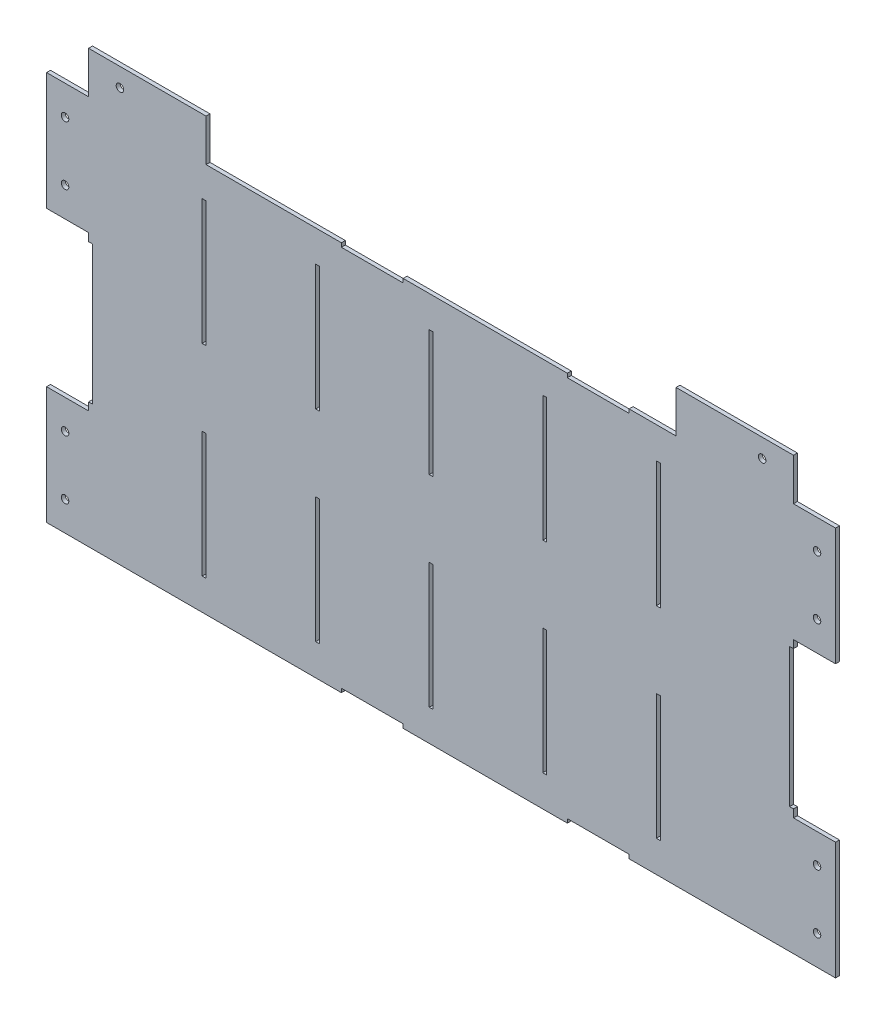
SolidWorks part; units mm, degrees
material "6061-T6 (SS)"
ref_plane "X-Y Datum" through (0, 0, 0) normal (0, 0, 1) x (1, 0, 0)
ref_plane "X-Z Datum" through (0, 0, 0) normal (0, 1, 0) x (1, 0, 0)
ref_plane "Y-Z Datum" through (0, 0, 0) normal (1, 0, 0) x (0, 0, -1)
sketch "Sketch1" plane through (0, 0, 0) normal (0, 0, 1) x (1, 0, 0)
  line L0 (-285.4305, 0) -> (285.4305, 0) construction
  line L1 (-285.4305, -157.7875) -> (285.4305, -157.7875)
  line L2 (-285.4305, -157.7875) -> (-285.4305, 157.7875)
  line L3 (-285.4305, 157.7875) -> (285.4305, 157.7875)
  line L4 (285.4305, -157.7875) -> (285.4305, 157.7875)
  line L5 (-285.4305, -157.7875) -> (285.4305, 157.7875) construction
  line L6 (-285.4305, 157.7875) -> (285.4305, -157.7875) construction
  line L7 (-282.2555, -154.615) -> (-282.2555, 154.615)
  line L8 (-280.6655, -153.025) -> (-195.0655, -153.025)
  line L9 (-280.6655, -153.025) -> (-280.6655, 153.025)
  line L10 (-280.6655, 153.025) -> (-195.0655, 153.025)
  line L11 (-195.0655, -153.025) -> (-195.0655, 153.025)
  line L12 (-280.6655, -153.025) -> (-195.0655, 153.025) construction
  line L13 (-280.6655, 153.025) -> (-195.0655, -153.025) construction
  line L14 (-282.2555, 154.615) -> (-193.4755, 154.615)
  line L15 (-193.4755, -154.615) -> (-193.4755, 154.615)
  line L16 (-282.2555, -154.615) -> (-193.4755, -154.615)
  line L17 (-190.3005, 154.615) -> (-101.5205, 154.615)
  line L18 (-188.7105, 153.025) -> (-103.1105, 153.025)
  line L19 (-190.3005, -154.615) -> (-190.3005, 154.615)
  line L20 (-188.7105, -153.025) -> (-188.7105, 153.025)
  line L21 (-101.5205, -154.615) -> (-101.5205, 154.615)
  line L22 (-103.1105, -153.025) -> (-103.1105, 153.025)
  line L23 (-188.7105, -153.025) -> (-103.1105, -153.025)
  line L24 (-190.3005, -154.615) -> (-101.5205, -154.615)
  line L25 (-188.7105, -153.025) -> (-103.1105, 153.025) construction
  line L26 (-188.7105, 153.025) -> (-103.1105, -153.025) construction
  line L27 (-98.3455, 154.615) -> (-9.5655, 154.615)
  line L28 (-96.7555, 153.025) -> (-11.1555, 153.025)
  line L29 (-98.3455, -154.615) -> (-98.3455, 154.615)
  line L30 (-96.7555, -153.025) -> (-96.7555, 153.025)
  line L31 (-9.5655, -154.615) -> (-9.5655, 154.615)
  line L32 (-11.1555, -153.025) -> (-11.1555, 153.025)
  line L33 (-96.7555, -153.025) -> (-11.1555, -153.025)
  line L34 (-98.3455, -154.615) -> (-9.5655, -154.615)
  line L35 (-96.7555, -153.025) -> (-11.1555, 153.025) construction
  line L36 (-96.7555, 153.025) -> (-11.1555, -153.025) construction
  line L37 (-6.3905, 154.615) -> (82.3895, 154.615)
  line L38 (-4.8005, 153.025) -> (80.7995, 153.025)
  line L39 (-6.3905, -154.615) -> (-6.3905, 154.615)
  line L40 (-4.8005, -153.025) -> (-4.8005, 153.025)
  line L41 (82.3895, -154.615) -> (82.3895, 154.615)
  line L42 (80.7995, -153.025) -> (80.7995, 153.025)
  line L43 (-4.8005, -153.025) -> (80.7995, -153.025)
  line L44 (-6.3905, -154.615) -> (82.3895, -154.615)
  line L45 (-4.8005, -153.025) -> (80.7995, 153.025) construction
  line L46 (-4.8005, 153.025) -> (80.7995, -153.025) construction
  line L47 (85.5645, 154.615) -> (174.3445, 154.615)
  line L48 (87.1545, 153.025) -> (172.7545, 153.025)
  line L49 (85.5645, -154.615) -> (85.5645, 154.615)
  line L50 (87.1545, -153.025) -> (87.1545, 153.025)
  line L51 (174.3445, -154.615) -> (174.3445, 154.615)
  line L52 (172.7545, -153.025) -> (172.7545, 153.025)
  line L53 (87.1545, -153.025) -> (172.7545, -153.025)
  line L54 (85.5645, -154.615) -> (174.3445, -154.615)
  line L55 (87.1545, -153.025) -> (172.7545, 153.025) construction
  line L56 (87.1545, 153.025) -> (172.7545, -153.025) construction
  point P0 (0, 0)
  point P8 (-237.8655, 0)
  point P17 (-145.9105, 0)
  dimension "D1" = 570.861
  dimension "D2" = 315.575
  dimension "D3" = 306.05
  dimension "D4" = 85.6
  dimension "D5" = 3.175
  dimension "D8" = 3.175
  dimension "D9" = 91.955
  dimension "D6" = 1.59
  dimension "D7" = 5
extrude "Boss-Extrude1" add sketch "Sketch1" along normal blind 3.175 contours L8 L11 L10 L9 | L20 L23 L22 L18 | L30 L33 L32 L28 | L50 L53 L52 L48 | L49 L54 L51 L47 L53 L50 L48 L52 | L1 L4 L3 L2 L54 L49 L47 L51 L44 L39 L37 L41 L34 L29 L27 L31 L24 L19 L17 L21 L16 L7 L14 L15 | L40 L43 L42 L38 | L7 L16 L15 L14 L11 L8 L9 L10 | L19 L24 L21 L17 L23 L20 L18 L22 | L29 L34 L31 L27 L33 L30 L28 L32 | L39 L44 L41 L37 L43 L40 L38 L42 region at (-284.7782, 0, 0) region at (-281.9338, 0, 0) region at (-237.8655, 0, 0) region at (-145.9105, 154.2933, 0) region at (-145.9105, 0, 0) region at (-53.9555, 154.2933, 0) region at (-53.9555, 0, 0) region at (37.9995, 154.2933, 0) region at (37.9995, 0, 0) region at (129.9545, 154.2933, 0) region at (129.9545, 0, 0)
sketch "Sketch2" plane through (0, 0, 3.175) normal (0, 0, 1) x (1, 0, 0)
  line L0 (-190.3005, -154.615) -> (-193.4755, -154.615) construction
  line L1 (-191.888, -154.615) -> (-191.888, 157.7875) construction
  line L2 (-285.4305, 157.7875) -> (285.4305, 157.7875) construction
  line L4 (-193.4755, -30.7875) -> (-190.3005, -30.7875)
  line L5 (-193.4755, -30.7875) -> (-193.4755, -132.3875)
  line L6 (-193.4755, -132.3875) -> (-190.3005, -132.3875)
  line L7 (-190.3005, -30.7875) -> (-190.3005, -132.3875)
  line L8 (-193.4755, -30.7875) -> (-190.3005, -132.3875) construction
  line L9 (-193.4755, -132.3875) -> (-190.3005, -30.7875) construction
  line L12 (-285.4305, -157.7875) -> (285.4305, -157.7875) construction
  point P8 (-191.888, -81.5875)
  dimension "D1" = 76.2
  dimension "D2" = 3.175
  dimension "D3" = 101.6
extrude "Cut-Extrude1" cut sketch "Sketch2" against normal blind 3.175
sketch "Sketch7" plane through (0, 0, 3.175) normal (0, 0, 1) x (1, 0, 0)
  line L0 (285.4305, -157.7875) -> (285.4305, 157.7875) construction
  line L1 (102.3049, -154.6125) -> (152.3049, -154.6125)
  line L2 (102.3049, -154.6125) -> (102.3049, -157.7875)
  line L3 (102.3049, -157.7875) -> (152.3049, -157.7875)
  line L4 (152.3049, -154.6125) -> (152.3049, -157.7875)
  line L5 (-80.6951, -154.6125) -> (-30.6951, -154.6125)
  line L6 (-80.6951, -154.6125) -> (-80.6951, -157.7875)
  line L7 (-80.6951, -157.7875) -> (-30.6951, -157.7875)
  line L8 (-30.6951, -154.6125) -> (-30.6951, -157.7875)
  dimension "D1" = 133
  dimension "D2" = 50
  dimension "D3" = 3.175
  dimension "D4" = 50
  dimension "D5" = 133.1256
extrude "Cut-Extrude5" cut sketch "Sketch7" against normal blind 3.175
mirror "Mirror3" about plane through (0, 0, 0) normal (0, 1, 0) of "Cut-Extrude1"
pattern_linear "LPattern2" count 5 spacing 91.96 along (1, 0, 0) of "Mirror3"
sketch "Sketch9" plane through (0, 0, 0) normal (0, 0, -1) x (-1, 0, 0)
  line L0 (-304.4805, -62.5375) -> (-304.4805, -157.7875) construction
  line L9 (-285.4305, 157.7875) -> (-190.3024, 157.7875)
  line L10 (-285.4305, 157.7875) -> (-285.4305, 191.8235)
  line L11 (-285.4305, 191.8235) -> (-190.3024, 191.8235)
  line L12 (-190.3024, 157.7875) -> (-190.3024, 191.8235)
  line L13 (-285.4305, 157.7875) -> (-323.5305, 157.7875)
  line L14 (-285.4305, 157.7875) -> (-285.4305, 62.5375)
  line L15 (-285.4305, 62.5375) -> (-323.5305, 62.5375)
  line L18 (-323.5305, 110.1625) -> (-285.4305, 110.1625) construction
  line L20 (-285.4305, -157.7875) -> (-323.5305, -157.7875)
  line L26 (-285.4305, -62.5375) -> (-323.5305, -62.5375)
  line L28 (-323.5305, -106.9875) -> (-323.5305, -157.7875) construction
  line L29 (-323.5305, -106.9875) -> (-285.4305, -106.9875) construction
  line L30 (-304.4805, -62.5375) -> (-304.4805, -110.1625) construction
  line L31 (-304.4805, -110.1625) -> (-304.4805, -157.7875) construction
  line L32 (-304.4805, -62.5375) -> (-304.4805, -110.1625) construction
  line L33 (-304.4805, -110.1625) -> (-304.4805, -157.7875) construction
  line L35 (-323.5305, 62.5375) -> (-323.5305, 157.7875) construction
  line L36 (-319.4665, 157.7875) -> (-319.4665, 62.5375)
  line L37 (-323.5305, -62.5375) -> (-323.5305, -157.7875) construction
  line L40 (-304.4805, 157.7875) -> (-304.4805, 110.1625) construction
  line L41 (-304.4805, 110.1625) -> (-304.4805, 62.5375) construction
  line L42 (-319.4665, -62.5375) -> (-319.4665, -157.7875)
  line L43 (-304.4805, 110.1625) -> (-304.4805, 62.5375) construction
  line L44 (-304.4805, -62.5375) -> (-304.4805, -110.1625) construction
  line L45 (-304.4805, -110.1625) -> (-304.4805, -157.7875) construction
  line L46 (-285.4305, -62.5375) -> (-285.4305, -157.7875)
  line L47 (-285.4305, 176.8375) -> (-190.3024, 176.8375) construction
  line L48 (-285.4305, 176.8375) -> (-260.0305, 176.8375) construction
  line L49 (-234.6305, 191.8235) -> (-234.6305, 157.7875) construction
  circle A4 centre (-304.4805, 133.975) radius 3.048
  circle A6 centre (-304.4805, 86.35) radius 3.048
  circle A7 centre (-304.4805, -86.35) radius 3.048
  circle A8 centre (-304.4805, -133.975) radius 3.048
  circle A10 centre (-260.0305, 176.8375) radius 3.048
  point P22 (-307.5285, 133.975)
  point P39 (-260.0305, 179.8855)
  dimension "D1" = 11.938
  dimension "D2" = 95.25
  dimension "D6" = 6.096
  dimension "D7" = 95.25
  dimension "D8" = 6.096
  dimension "D9" = 6.096
  dimension "D10" = 6.096
  dimension "D12" = 19.05
  dimension "D13" = 11.938
  dimension "D11" = 25.4
  dimension "D3" = 95.1281
  dimension "D4" = 34.036
  dimension "D5" = 19.05
  dimension "D14" = 25.4
extrude "Boss-Extrude3" add sketch "Sketch9" against normal blind 3.175 contours L13 L15 L14 | L9 L12 L11 L10 | L26 L28 L20 A8 A7 region at (237.6648, 174.787, 0) region at (302.4112, 110.1625, 0) region at (302.4112, -110.1625, 0)
mirror "Mirror4" about plane through (0, 0, 0) normal (1, 0, 0) of "Boss-Extrude3"
mirror "Mirror5" about plane through (0, 0, 0) normal (0, 1, 0) of "Cut-Extrude5"
sketch "Sketch10" plane through (0, 0, 0) normal (0, 0, -1) x (-1, 0, 0)
  line L0 (-285.4305, 62.5375) -> (-285.4305, 56.1875)
  line L1 (-285.4305, -62.5375) -> (-285.4305, 62.5375) construction
  line L2 (-285.4305, -62.5375) -> (-319.4665, -62.5375) construction
  line L3 (-285.4305, 56.1875) -> (-282.2555, 56.1875)
  line L4 (-285.4305, 56.1875) -> (-285.4305, -56.1875)
  line L5 (-285.4305, -56.1875) -> (-282.2555, -56.1875)
  line L6 (-282.2555, 56.1875) -> (-282.2555, -56.1875)
  line L7 (-285.4305, 62.5375) -> (-319.4665, 62.5375) construction
  dimension "D1" = 6.35
  dimension "D2" = 3.175
  dimension "D3" = 6.35
extrude "Cut-Extrude6" cut sketch "Sketch10" against normal through all contours L6 L3 L4 L5 region at (283.843, 0, 0)
mirror "Mirror6" about plane through (0, 0, 0) normal (1, 0, 0) of "Cut-Extrude6"
